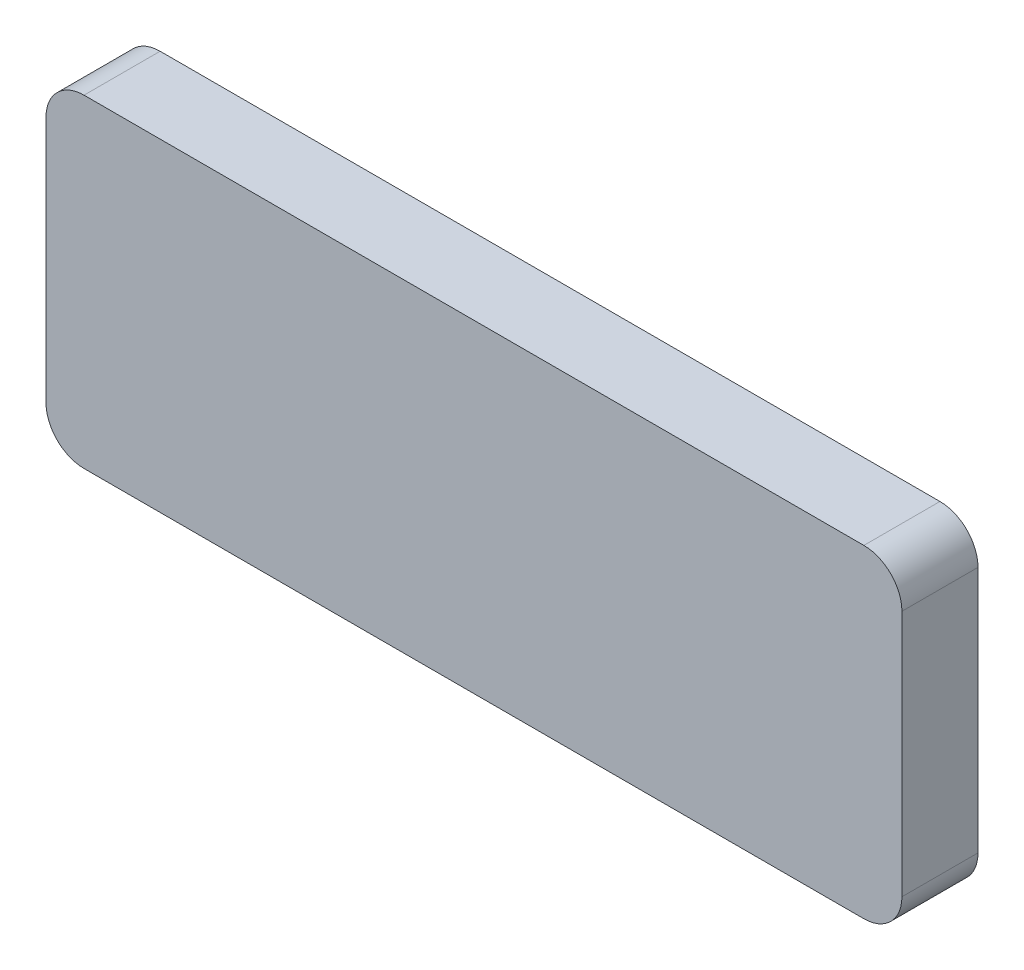
SolidWorks part; units mm, degrees
ref_plane "Front Plane" through (0, 0, 0) normal (0, 0, 1) x (1, 0, 0)
ref_plane "Top Plane" through (0, 0, 0) normal (0, 1, 0) x (1, 0, 0)
ref_plane "Right Plane" through (0, 0, 0) normal (1, 0, 0) x (0, 0, -1)
sketch "Sketch1" plane through (0, 0, 0) normal (0, 0, 1) x (1, 0, 0)
  line L0 (71.4375, -20.6375) -> (71.4375, 20.6375)
  line L1 (-69.85, -25.4) -> (69.85, -25.4) construction
  line L2 (-69.85, -25.4) -> (-69.85, 25.4) construction
  line L3 (-69.85, 25.4) -> (69.85, 25.4) construction
  line L4 (69.85, -25.4) -> (69.85, 25.4) construction
  line L5 (-69.85, -25.4) -> (69.85, 25.4) construction
  line L6 (-69.85, 25.4) -> (69.85, -25.4) construction
  line L7 (-65.0875, 26.9875) -> (65.0875, 26.9875)
  line L8 (-71.4375, -20.6375) -> (-71.4375, 20.6375)
  line L9 (-65.0875, -26.9875) -> (65.0875, -26.9875)
  line L10 (-71.4375, 26.9875) -> (71.4375, 26.9875) construction
  line L11 (-71.4375, -26.9875) -> (-71.4375, 26.9875) construction
  line L12 (-71.4375, -26.9875) -> (71.4375, -26.9875) construction
  line L13 (71.4375, -26.9875) -> (71.4375, 26.9875) construction
  arc A0 (-65.0875, 26.9875) -> (-71.4375, 20.6375) centre (-65.0875, 20.6375) ccw
  arc A1 (-71.4375, -20.6375) -> (-65.0875, -26.9875) centre (-65.0875, -20.6375) ccw
  arc A2 (71.4375, -20.6375) -> (65.0875, -26.9875) centre (65.0875, -20.6375) cw
  arc A3 (71.4375, 20.6375) -> (65.0875, 26.9875) centre (65.0875, 20.6375) ccw
  point P0 (0, 0)
  dimension "D4" = 6.35
  dimension "D1" = 50.8
  dimension "D2" = 139.7
  dimension "D3" = 1.5875
extrude "Boss-Extrude1" add sketch "Sketch1" against normal blind 12.7
